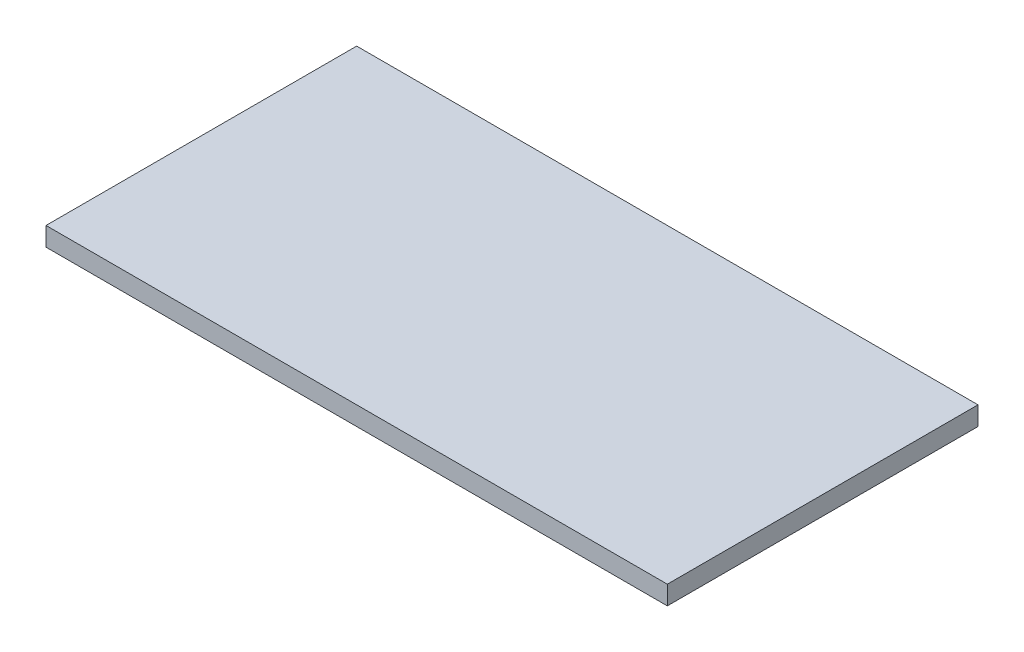
SolidWorks part; units mm, degrees
ref_plane "Front Plane" through (0, 0, 0) normal (0, 0, 1) x (1, 0, 0)
ref_plane "Top Plane" through (0, 0, 0) normal (0, 1, 0) x (1, 0, 0)
ref_plane "Right Plane" through (0, 0, 0) normal (1, 0, 0) x (0, 0, -1)
sketch "Sketch1" plane through (0, 0, 0) normal (0, 1, 0) x (1, 0, 0)
  line L1 (0, 5) -> (15, 5)
  line L2 (0, 5) -> (0, -5)
  line L3 (0, -5) -> (15, -5)
  line L4 (15, 5) -> (15, -5)
  point P4 (0, 0)
  dimension "D1" = 15
  dimension "D2" = 10
extrude "Boss-Extrude1" add sketch "Sketch1" along normal blind 3 and the other way blind 4
sketch "Sketch2" plane through (0, 0, 0) normal (1, 0, 0) x (0, 0, -1)
  circle A0 centre (0, 0) radius 2.3
  circle A1 centre (0, 0) radius 3.025
  dimension "D1" = 4.6
  dimension "D2" = 6.05
extrude "Cut-Extrude3" cut sketch "Sketch2" along normal blind 10 contours A0
extrude "Cut-Extrude4" cut sketch "Sketch2<4>" along normal blind 2.6
sketch "Sketch2<4>" plane through (0, 0, 0) normal (1, 0, 0) x (0, 0, -1) same geometry as "Sketch2"
extrude "Cut-Extrude5" cut sketch "Sketch2<5>" along normal up to surface (10 mm away) from offset 6.44 up to face at (10, 0, -2.3)
sketch "Sketch2<5>" plane through (0, 0, 0) normal (1, 0, 0) x (0, 0, -1) same geometry as "Sketch2"
fillet "Fillet1" radius 1 1 edges at (2.6, 0, -2.3)
sketch "Sketch3" plane through (0, 3, 0) normal (0, 1, 0) x (1, 0, 0)
  line L0 (15, 0) -> (0, 0) construction
  line L1 (0, 16.5) -> (66, 16.5)
  line L2 (0, 16.5) -> (0, -16.5)
  line L3 (0, -16.5) -> (66, -16.5)
  line L4 (66, 16.5) -> (66, -16.5)
  line L5 (15, -5) -> (15, 5) construction
  line L6 (0, 5) -> (0, 0.3881) construction
  point P9 (0, 0)
  dimension "D1" = 33
  dimension "D2" = 66
extrude "Boss-Extrude2" add sketch "Sketch3" along normal blind 2
fillet "Fillet2" radius 3 3 edges at (7.5, 3, -5) (7.5, 3, 5) (15, 3, 0)
fillet "Fillet3" radius 3 3 edges at (15, -4, 0) (7.5, -4, -5) (7.5, -4, 5)
